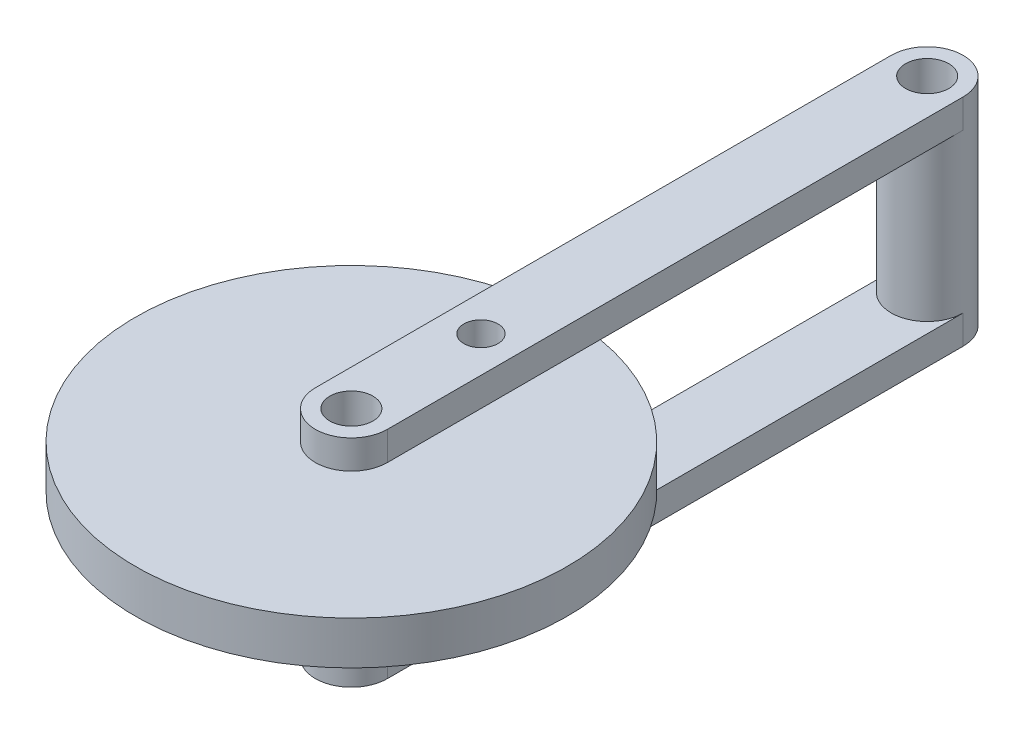
SolidWorks part; units mm, degrees
material "ABS"
ref_plane "Front Plane" through (0, 0, 0) normal (0, 0, 1) x (1, 0, 0)
ref_plane "Top Plane" through (0, 0, 0) normal (0, 1, 0) x (1, 0, 0)
ref_plane "Right Plane" through (0, 0, 0) normal (1, 0, 0) x (0, 0, -1)
sketch "Sketch1" plane through (0, 0, 0) normal (0, 1, 0) x (1, 0, 0)
  line L0 (0, 0) -> (0, -40) construction
  line L1 (2.5, 0) -> (2.5, -40)
  line L2 (-2.5, 0) -> (-2.5, -40)
  arc A0 (2.5, 0) -> (-2.5, 0) centre (0, 0) ccw
  arc A1 (-2.5, -40) -> (2.5, -40) centre (0, -40) ccw
  point P3 (0, -20)
  dimension "D2" = 2.5
  dimension "D1" = 40
extrude "Boss-Extrude1" add sketch "Sketch1" along normal blind 2 contours L1 A1 L2 A0
sketch "Sketch2" plane through (0, 2, 0) normal (0, 1, 0) x (1, 0, 0)
  circle A0 centre (0, 0) radius 2.5
  dimension "D1" = 5
extrude "Boss-Extrude2" add sketch "Sketch2" along normal blind 11
extrude "Boss-Extrude3" add sketch "Sketch1<3>" along normal blind 2 from offset 13
sketch "Sketch1<3>" plane through (0, 0, 0) normal (0, 1, 0) x (1, 0, 0) same geometry as "Sketch1"
sketch "Sketch7" plane through (0, 13, 0) normal (0, -1, 0) x (1, 0, 0)
  circle A0 centre (0, 40) radius 15
  dimension "D1" = 30
extrude "Boss-Extrude5" add sketch "Sketch7" along normal blind 3
hole_wizard "Ø3.0mm Clearance Dowel Hole1" positions "Sketch4" profile "Sketch5" hole size "Ø3.0" standard "ANSI Metric" end condition through all
sketch "Sketch4" plane through (0, 15, 0) normal (0, 1, 0) x (1, 0, 0)
  point P0 (0, 0)
  point P3 (0, -40)
sketch "Sketch5" plane through (0, 15, 0) normal (1, 0, 0) x (0, 0, 1)
  line L0 (0, 0) -> (0, 15)
  line L1 (0, 15) -> (1.5, 15)
  line L2 (1.5, 15) -> (1.5, 0)
  line L5 (1.5, 0) -> (0, 0)
  line L11 (0, -6.35) -> (0, 107.95) construction
  dimension "Thru Hole Dia." = 3
  dimension "Thru Hole Depth" = 15
hole_wizard "#4-48 Tapped Hole1" positions "Sketch11" profile "Sketch9" tap size "#4-48" standard "ANSI Inch"
sketch "Sketch11" plane through (0, 15, 0) normal (0, 1, 0) x (1, 0, 0)
  line L0 (0, 0) -> (0, -40) construction
  point P0 (0, -31)
  dimension "D1" = 9
sketch "Sketch9" plane through (0, 15, 31) normal (1, 0, 0) x (0, 0, 1)
  line L0 (0, 0) -> (0, 7.9835)
  line L1 (0, 7.9835) -> (1.1874, 7.27)
  line L2 (1.1874, 7.27) -> (1.1874, 0)
  line L5 (1.1874, 0) -> (0, 0)
  line L10 (0, 7.9835) -> (-1.1875, 7.27) construction
  line L11 (0, -6.35) -> (0, 107.95) construction
  dimension "Tap Drill Dia." = 2.3749
  dimension "Tap Drill Depth" = 7.27
  dimension "Drill Angle" = 118
cosmetic thread "Hole Thread1" parameters "D1"=5, "D2"=2.8448
